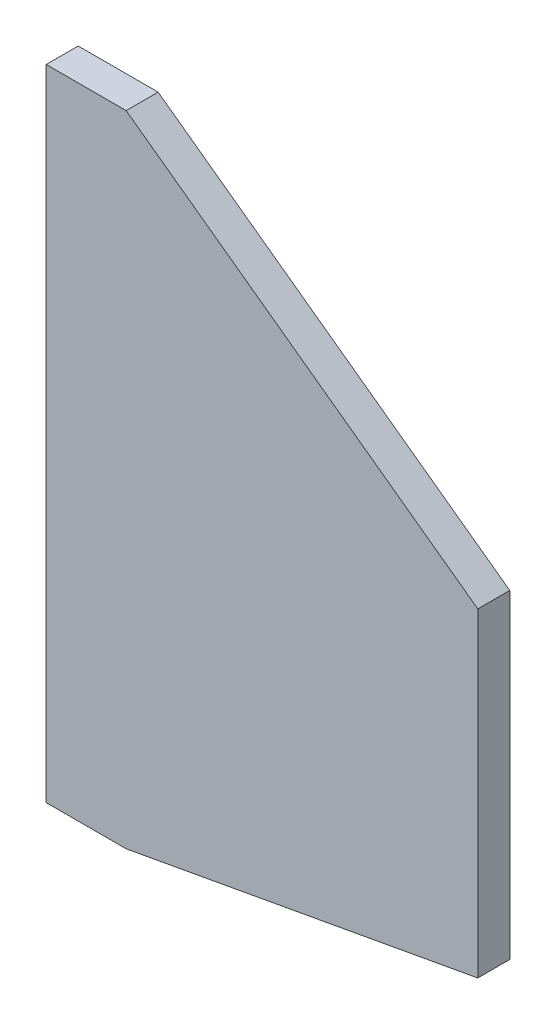
SolidWorks part; units mm, degrees
material "Beech"
ref_plane "Front Plane" through (0, 0, 0) normal (0, 0, 1) x (1, 0, 0)
ref_plane "Top Plane" through (0, 0, 0) normal (0, 1, 0) x (1, 0, 0)
ref_plane "Right Plane" through (0, 0, 0) normal (1, 0, 0) x (0, 0, -1)
sketch "Sketch2" plane through (0, 0, 0) normal (0, 0, 1) x (1, 0, 0)
  line L0 (0, 0) -> (12.7, 0)
  line L1 (12.7, 0) -> (68.58, 10.16)
  line L2 (68.58, 10.16) -> (68.58, 60.96)
  line L3 (68.58, 60.96) -> (12.7, 101.6)
  line L4 (12.7, 101.6) -> (0, 101.6)
  line L5 (0, 101.6) -> (0, 0)
  dimension "D1" = 101.6
  dimension "D2" = 55.88
  dimension "D3" = 50.8
  dimension "D4" = 40.64
  dimension "D5" = 12.7
extrude "Boss-Extrude1" add sketch "Sketch2" along normal blind 5.08
